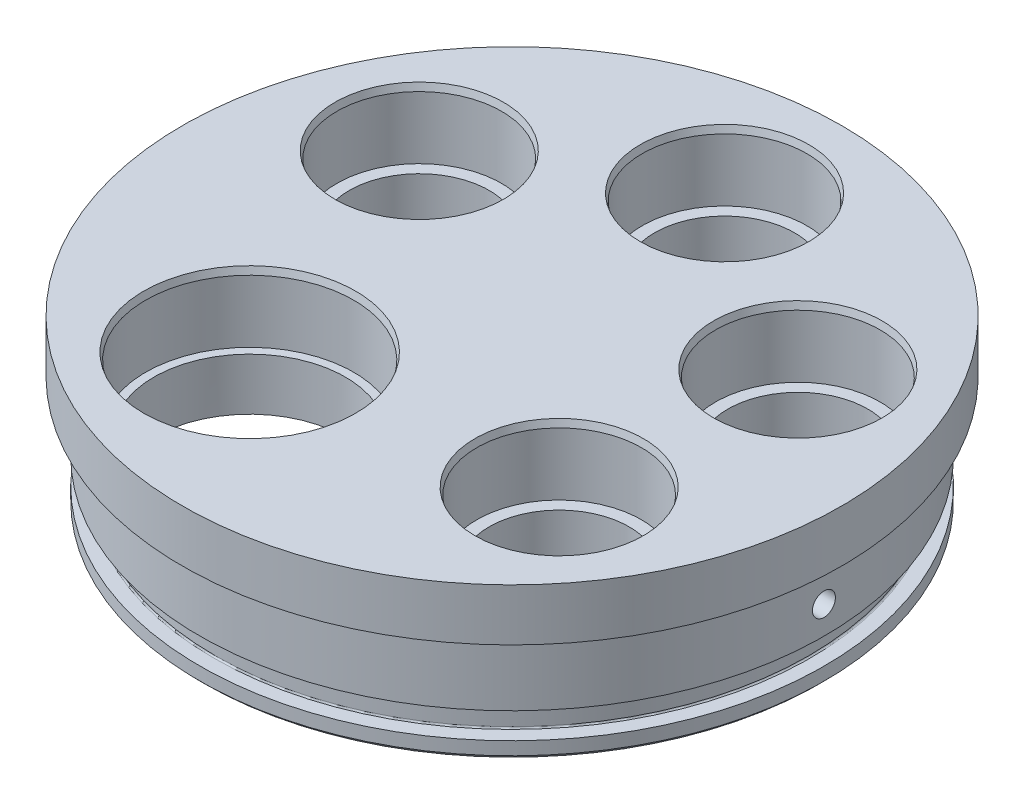
SolidWorks part; units mm, degrees
material "PET-P _ White"
ref_plane "Front Plane" through (0, 0, 0) normal (0, 0, 1) x (1, 0, 0)
ref_plane "Top Plane" through (0, 0, 0) normal (0, 1, 0) x (1, 0, 0)
ref_plane "Right Plane" through (0, 0, 0) normal (1, 0, 0) x (0, 0, -1)
sketch "Sketch1" plane through (0, 0, 0) normal (0, 0, 1) x (1, 0, 0)
  line L0 (0, 0) -> (0, 50.9782) construction
  line L1 (17, 29.8788) -> (17, 0) construction
  line L2 (52.7431, 21.954) -> (52.7431, 29.8788)
  line L3 (52.7431, 21.954) -> (57.1246, 21.954)
  line L4 (57.1246, 21.954) -> (57.1246, 25.129)
  line L5 (57.1246, 42.5788) -> (60.325, 42.5788)
  line L6 (60.325, 42.5788) -> (60.325, 52.1038)
  line L7 (60.325, 52.1038) -> (0, 52.1038)
  line L8 (0, 52.1038) -> (0, 27.94) construction
  line L9 (57.1246, 25.129) -> (54.3306, 25.129)
  line L10 (54.3306, 25.129) -> (54.3306, 29.8788)
  line L11 (54.3306, 29.8788) -> (57.1246, 29.8788)
  line L12 (57.1246, 29.8788) -> (57.1246, 42.5788)
  line L13 (54.3306, 29.8788) -> (54.2671, 29.8788) construction
  line L14 (54.2671, 29.8788) -> (54.2671, 25.129) construction
  line L15 (54.2671, 25.129) -> (54.3306, 25.129) construction
  line L16 (54.2671, 27.5039) -> (55.9816, 27.5039) construction
  line L17 (55.9816, 27.5039) -> (56.1467, 27.5039) construction
  line L18 (57.15, 42.5788) -> (57.15, 21.954) construction
  line L19 (57.2262, 42.5788) -> (57.2262, 21.954) construction
  line L20 (57.6961, 27.5039) -> (57.6961, 25.129) construction
  line L21 (57.9628, 27.5039) -> (57.9628, 29.8788) construction
  line L22 (52.7431, 29.8788) -> (17, 29.8788)
  line L23 (17, 0) -> (12.7, 0) construction
  line L24 (12.7, 0) -> (12.7, 27.94) construction
  line L25 (12.7, 27.94) -> (0, 27.94) construction
  line L26 (17, 12.7) -> (0, 12.7) construction
  line L27 (17, 21.7) -> (21, 21.7) construction
  line L28 (21, 21.7) -> (21, 3.7) construction
  line L29 (21, 3.7) -> (17, 3.7) construction
  line L30 (12.7, 7.7) -> (17, 7.7) construction
  line L31 (17, 17.7) -> (12.7, 17.7) construction
  line L32 (17, 12.7) -> (21, 12.7) construction
  line L33 (17, 21.7) -> (17, 17.7) construction
  line L34 (17, 7.7) -> (17, 3.7) construction
  line L35 (57.1246, 34.9588) -> (49.7908, 34.9588) construction
  line L36 (57.1246, 36.9588) -> (49.7908, 36.9588) construction
  line L37 (21, 12.7) -> (61, 12.7) construction
  line L38 (0, 52.1038) -> (0, 29.8788)
  line L39 (0, 29.8788) -> (17, 29.8788)
  circle A0 centre (55.9816, 27.5039) radius 1.7145 construction
  circle A1 centre (56.1467, 27.5039) radius 1.8161 construction
  dimension "D1" = 3.6322
  dimension "D2" = 3.429
  dimension "D3" = 114.3
  dimension "D4" = 114.4524
  dimension "D5" = 0.0254
  dimension "D6" = 3.175
  dimension "D7" = 4.7498
  dimension "D8" = 3.175
  dimension "D9" = 9.525
  dimension "D11" = 12.7
  dimension "D12" = 12.7
  dimension "D13" = 18
  dimension "D14" = 4
  dimension "D15" = 10
  dimension "D16" = 15.24
  dimension "D17" = 0.254
  dimension "D18" = 17
  dimension "D19" = 4.3
  dimension "D20" = 7.62
  dimension "D21" = 5.08
  dimension "D22" = 4
  dimension "D23" = 1.5875
  dimension "D24" = 40
  dimension "D25" = 0.0635
  dimension "D26" = 108.6612
  dimension "D27" = 0.5461
  dimension "D28" = 0.8128
  dimension "D29" = 7.9248
revolve "Revolve1" add sketch "Sketch1" angle 360 about L0
fillet "Fillet1" radius 3.175 1 edges at (0, 29.8788, -52.7431)
sketch "Retaining hole" plane through (0, 0, 0) normal (1, 0, 0) x (0, 0, -1)
  line L0 (0, 0) -> (0, 34.9588) construction
  line L1 (-57.1246, 42.5788) -> (57.1246, 42.5788) construction
  circle A0 centre (0, 34.9588) radius 3.5
  dimension "D1" = 7
  dimension "D2" = 7.62
ref_plane "Plane1" through (57.1246, 0, 0) normal (1, 0, 0) x (0, 0, -1)
hole_wizard "Tapped Hole for M4x0.7 Helicoil1" positions "Sketch4" profile "Sketch5" tap size "M4x0.7" standard "Helicoil® Metric"
sketch "Sketch4" plane through (57.1246, 0, 0) normal (1, 0, 0) x (0, 0, -1)
  point P0 (0, 34.9588)
sketch "Sketch5" plane through (57.1246, 34.9588, 0) normal (0, 1, 0) x (0, 0, -1)
  line L0 (0, 0) -> (0, 11.4624)
  line L1 (0, 11.4624) -> (2.1, 10.2006)
  line L2 (2.1, 10.2006) -> (2.1, 0)
  line L5 (2.1, 0) -> (0, 0)
  line L10 (0, 11.4624) -> (-2.1, 10.2006) construction
  line L11 (0, -6.35) -> (0, 107.95) construction
  dimension "Tap Drill Dia." = 4.2
  dimension "Tap Drill Depth" = 10.2006
  dimension "Drill Angle" = 118
cosmetic thread "Hole Thread1" parameters "D1"=4.699, "D2"=5.007
pattern_circular "M4 CirPattern1" count 2 over 360 about axis through (0, 0, 0) along (0, -1, 0) of "Tapped Hole for M4x0.7 Helicoil1"
sketch "FeedThru Layout" plane through (0, 52.1038, 0) normal (0, 1, 0) x (1, 0, 0)
  line L0 (-13.8632, -8.1915) -> (1.3314, -19.6819) construction
  line L1 (-28.3442, -10.2016) -> (-39.8345, -25.3961) construction
  line L2 (3.3415, -34.1629) -> (-8.1489, -49.3574) construction
  line L3 (-37.8244, -39.8771) -> (-22.6299, -51.3675) construction
  line L4 (-34.0894, -17.7989) -> (-2.4037, -41.7602) construction
  line L5 (0, 53.975) -> (0, 57.1246) construction
  line L7 (0, 0) -> (-18.2465, -29.7795) construction
  line L8 (-18.2465, -29.7795) -> (-28.1992, -46.0229) construction
  line L9 (-28.1992, -46.0229) -> (-29.8447, -48.7085) construction
  circle A0 centre (0, 0) radius 38.8938 construction
  circle A1 centre (-34.6525, 17.6614) radius 15.0749
  circle A2 centre (0, 38.8937) radius 15.0813
  circle A3 centre (34.6525, 17.6614) radius 15.0749
  circle A4 centre (31.471, -22.8539) radius 15.0749
  circle A5 centre (-34.6525, 17.6614) radius 20.32 construction
  circle A6 centre (0, 38.8937) radius 20.32 construction
  circle A7 centre (34.6525, 17.6614) radius 20.32 construction
  circle A8 centre (31.471, -22.8539) radius 20.32 construction
  circle A9 centre (-18.2465, -29.7795) radius 9.525
  circle A10 centre (0, 38.8937) radius 11.115 construction
  circle A11 centre (0, 0) radius 25.4 construction
  circle A12 centre (-18.2465, -29.7795) radius 19.05
  circle A13 centre (-18.2465, -29.7795) radius 23.8082 construction
  arc A14 (-22.6299, -51.3675) -> (-8.1489, -49.3574) centre (-16.3945, -43.122) ccw construction
  circle A15 centre (-18.2465, -29.7795) radius 35.1227
  arc A17 (3.3415, -34.1629) -> (1.3314, -19.6819) centre (-4.9041, -27.9275) ccw construction
  arc A18 (-13.8632, -8.1915) -> (-28.3442, -10.2016) centre (-20.0986, -16.4371) ccw construction
  arc A19 (-39.8345, -25.3961) -> (-37.8244, -39.8771) centre (-31.589, -31.6316) ccw construction
  circle A21 centre (0, 0) radius 57.1246 construction
  circle A22 centre (0, 0) radius 12.7
  point P42 (9.5769, -25.9173)
  point P45 (-22.1087, -1.9561)
  point P52 (-18.2465, -29.7795)
  dimension "D1" = 30.1498
  dimension "D2" = 5.2451
  dimension "D3" = 22.23
  dimension "D4" = 50.8
  dimension "D5" = 30.1625
  dimension "D6" = 19.05
  dimension "D7" = 34.925
  dimension "D8" = 38.1
  dimension "D10" = 10.3378
  dimension "D11" = 47.6164
  dimension "D12" = 77.7875
  dimension "D16" = 25.4
  dimension "D17" = 40.64
  dimension "D9" = 39.7256
sketch "Sketch6" plane through (0, 52.1038, 0) normal (0, 1, 0) x (1, 0, 0)
  circle A0 centre (0, 38.8937) radius 15.0749
  circle A1 centre (34.6525, 17.6614) radius 15.0749
  circle A2 centre (-34.6525, 17.6614) radius 15.0749
  circle A3 centre (31.471, -22.8539) radius 15.0749
  circle A4 centre (31.471, -22.8539) radius 15.0749 construction
extrude "0.88 feedthru Cut-Extrude2" cut sketch "Sketch6" against normal blind 12.7
sketch "Sketch7" plane through (0, 39.4038, 0) normal (0, 1, 0) x (1, 0, 0)
  circle A0 centre (0, 38.8937) radius 12.827
  circle A1 centre (34.6525, 17.6614) radius 12.827
  circle A2 centre (-34.6525, 17.6614) radius 12.827
  circle A3 centre (31.471, -22.8539) radius 12.827
  dimension "D1" = 25.654
extrude "0.88 feedthru Cut-Extrude3" cut sketch "Sketch7" against normal through all
sketch "Sketch8" plane through (0, 52.1038, 0) normal (0, 1, 0) x (1, 0, 0)
  circle A0 centre (-18.2465, -29.7795) radius 19.05
  circle A1 centre (-18.2465, -29.7795) radius 19.05 construction
  dimension "D1" = 38.1
extrude "1.5 feedthru Cut-Extrude4" cut sketch "Sketch8" against normal blind 12.7
sketch "Sketch9" plane through (0, 39.4038, 0) normal (0, 1, 0) x (1, 0, 0)
  circle A0 centre (-18.2465, -29.7795) radius 17.526
  dimension "D1" = 35.052
extrude "1.5 feedthru Cut-Extrude5" cut sketch "Sketch9" against normal through all
hole_wizard "M27x3 Tapped Hole1" positions "Sketch22" profile "Sketch23" tap size "M27x2.0" standard "ANSI Metric"
sketch "Sketch22" plane through (0, 29.8788, 0) normal (0, -1, 0) x (-1, 0, 0)
  point P0 (0, 0)
sketch "Sketch23" plane through (0, 29.8788, 0) normal (1, 0, 0) x (0, 0, -1)
  line L0 (0, 0) -> (0, 12.7)
  line L1 (0, 12.7) -> (12.5, 12.7)
  line L2 (12.5, 12.7) -> (12.5, 0)
  line L5 (12.5, 0) -> (0, 0)
  line L10 (0, 12.7) -> (-12.5, 12.7) construction
  line L11 (0, -6.35) -> (0, 107.95) construction
  dimension "Tap Drill Dia." = 25
  dimension "Tap Drill Depth" = 12.7
  dimension "Drill Angle" = 180
cosmetic thread "Hole Thread6" parameters "D1"=11.43, "D2"=27
ref_plane "Plane2" through (0, 50.5163, 0) normal (0, 1, 0) x (1, 0, 0)
sketch "Sketch19" [suppressed] plane through (0, 29.8788, 0) normal (0, -1, 0) x (1, 0, 0)
  circle A0 centre (0, 0) radius 12.126
  dimension "D1" = 24.252
extrude "thread shear area Cut-Extrude8" [suppressed] cut sketch "Sketch19" against normal blind 14.224
sketch "Sketch17" [suppressed] plane through (0, 21.954, 0) normal (0, -1, 0) x (1, 0, 0)
  circle A0 centre (0, 0) radius 12.658
  dimension "D1" = 25.316
curve "thread shear area Helix/Spiral1" [suppressed] pitch 3 height 51 turns 17
sketch "Sketch18" [suppressed] plane through (0, 0, 0) normal (0, 0, 1) x (1, 0, 0)
  line L0 (11.1422, 23.7042) -> (13.849, 22.1415)
  line L1 (13.849, 22.1415) -> (13.849, 21.7665)
  line L2 (13.849, 21.7665) -> (11.1422, 20.2038)
  line L3 (11.1422, 20.2038) -> (11.1422, 23.7042)
  line L4 (14.1738, 21.954) -> (11.1422, 21.954) construction
  line L5 (0, 26.8435) -> (0, 32.3406) construction
  line L6 (0, 29.8788) -> (0, 21.954) construction
  line L7 (0, 42.5788) -> (0, 29.8788) construction
  line L8 (13.849, 22.1415) -> (14.1738, 21.954) construction
  line L9 (14.1738, 21.954) -> (13.849, 21.7665) construction
  line L10 (-12.658, 21.954) -> (12.658, 21.954) construction
  point P3 (12.658, 21.954)
  dimension "D1" = 27.698
  dimension "D2" = 60
  dimension "D4" = 0.3248
sweep "Thread shear area Cut-Sweep1" [suppressed] cut profiles "Sketch18" path "thread shear area Helix/Spiral1"
sketch "Sketch20" [suppressed] plane through (0, 29.8788, 0) normal (0, -1, 0) x (1, 0, 0)
  circle A0 centre (0, 0) radius 13.2885
  circle A1 centre (0, 0) radius 75.4493
  dimension "D1" = 26.577
extrude "Thread shear area Cut-Extrude9" [suppressed] cut sketch "Sketch20" against normal through all
sketch "Sketch21" [suppressed] plane through (0, 48.9288, 0) normal (0, 1, 0) x (1, 0, 0)
  circle A0 centre (0, 0) radius 22.3741
extrude "thread shear area Cut-Extrude10" [suppressed] cut sketch "Sketch21" against normal offset from surface (8.89 mm away) 10.16 up to face at (0, 29.8788, -12.5)
sketch "Main Circuit Board" plane through (0, 29.8788, 0) normal (0, -1, 0) x (1, 0, 0)
  line L0 (0, 0) -> (22.3935, -36.5476) construction
  line L1 (0, 0) -> (13.6028, 40.6467) construction
  line L2 (0, 0) -> (-42.3913, 6.3379) construction
  line L3 (0, 0) -> (60.325, 0) construction
  line L4 (16.6631, 37.1873) -> (18.129, 41.5673) construction
  line L5 (18.129, 41.5673) -> (15.0687, 45.0268) construction
  line L6 (15.0687, 45.0268) -> (10.5425, 44.1062) construction
  line L7 (10.5425, 44.1062) -> (9.0767, 39.7262) construction
  line L8 (9.0767, 39.7262) -> (12.137, 36.2667) construction
  line L9 (12.137, 36.2667) -> (16.6631, 37.1873) construction
  circle A0 centre (0, 0) radius 55.5625
  circle A1 centre (0, 0) radius 26.1937
  circle A2 centre (0, 0) radius 42.8625 construction
  circle A3 centre (13.6028, 40.6467) radius 4 construction
  circle A4 centre (13.6028, 40.6467) radius 4.6188 construction
  circle A6 centre (-42.3913, 6.3379) radius 4.6188 construction
  circle A7 centre (22.3935, -36.5476) radius 4.6188 construction
  circle A8 centre (0, 0) radius 60.325 construction
  circle A9 centre (22.3935, -36.5476) radius 9.689 construction
  arc A10 (47.2177, -15.0828) -> (39.9492, -29.3438) centre (34.6525, -17.6614) ccw construction
  arc A11 (8.0032, -48.9177) -> (-8.0032, -48.9177) centre (0, -38.8937) ccw construction
  circle A12 centre (34.6525, -17.6614) radius 14.2875
  circle A13 centre (0, -38.8937) radius 14.2875
  dimension "D1" = 52.3875
  dimension "D2" = 111.125
  dimension "D5" = 8
  dimension "D6" = 85.725
  dimension "D8" = 28.575
  dimension "D3" = 100
  dimension "D4" = 130
  dimension "D7" = 58.503
hole_wizard "M4x0.7 Tapped Hole1" positions "Sketch25" profile "Sketch26" tap size "M4x0.7" standard "ANSI Metric"
sketch "Sketch25" plane through (0, 29.8788, 0) normal (0, -1, 0) x (-1, 0, 0)
  line L0 (0, 0) -> (-22.3935, 36.5476) construction
  point P0 (-22.3935, 36.5476)
  point P4 (42.3913, -6.3379)
  point P7 (-13.6028, -40.6467)
sketch "Sketch26" plane through (22.3935, 29.8788, -36.5476) normal (1, 0, 0) x (0, 0, -1)
  line L0 (0, 0) -> (0, 13.092)
  line L1 (0, 13.092) -> (1.65, 12.1006)
  line L2 (1.65, 12.1006) -> (1.65, 0)
  line L5 (1.65, 0) -> (0, 0)
  line L10 (0, 13.092) -> (-1.65, 12.1006) construction
  line L11 (0, -6.35) -> (0, 107.95) construction
  dimension "Tap Drill Dia." = 3.3
  dimension "Tap Drill Depth" = 12.1006
  dimension "Drill Angle" = 118
cosmetic thread "Hole Thread3" parameters "D1"=10, "D2"=4
cosmetic thread "Hole Thread4" parameters "D1"=10, "D2"=4
cosmetic thread "Hole Thread5" parameters "D1"=10, "D2"=4
chamfer "Chamfer1" distance 0.7937 angle 45 1 edges at (0, 21.954, -57.1246)
fillet "Fillet2" radius 0.254 2 edges at (0, 25.129, -54.3306) (0, 29.8788, -54.3306)
chamfer "Chamfer2" distance 1.27 angle 15 5 edges at (-18.2465, 52.1038, 48.8295) (34.6525, 52.1038, -2.5865) (0, 52.1038, -23.8188) (-34.6525, 52.1038, -2.5865) (31.471, 52.1038, 37.9288) first distance on face at (-18.2465, 39.4038, 48.8295) first distance on face at (34.6525, 39.4038, -2.5865) first distance on face at (0, 39.4038, -23.8188) first distance on face at (-34.6525, 39.4038, -2.5865) first distance on face at (31.471, 39.4038, 37.9288)
